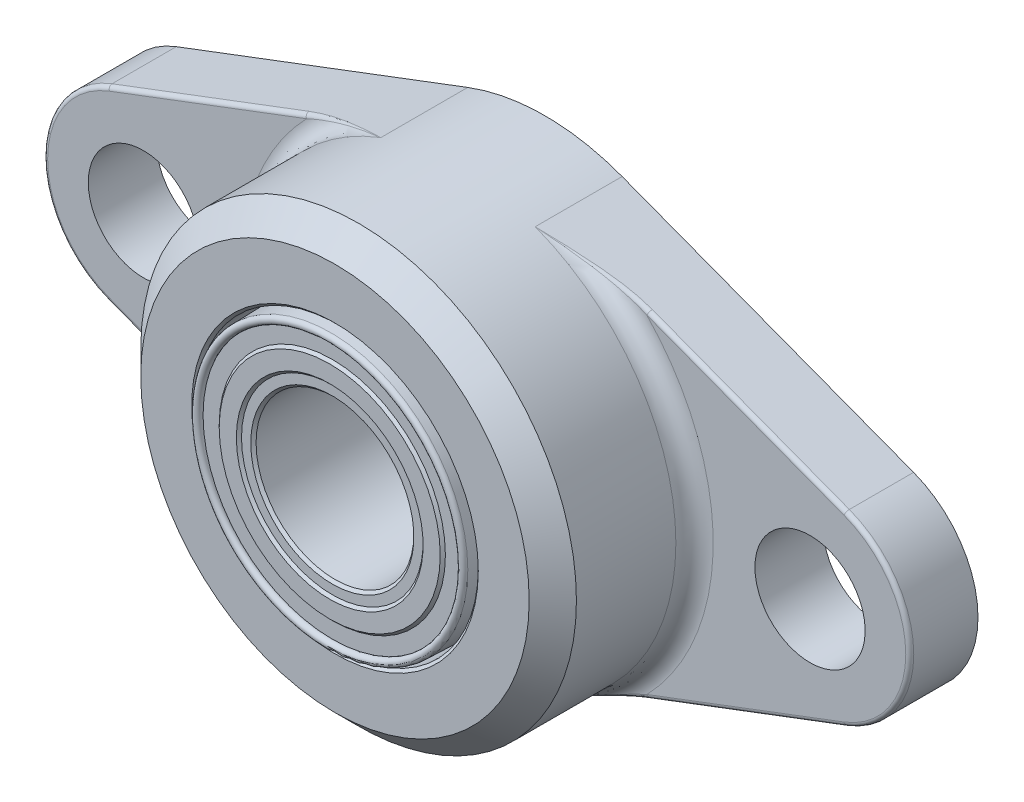
SolidWorks part; units mm, degrees
ref_plane "Front Plane" through (0, 0, 0) normal (0, 0, 1) x (1, 0, 0)
ref_plane "Top Plane" through (0, 0, 0) normal (0, 1, 0) x (1, 0, 0)
ref_plane "Right Plane" through (0, 0, 0) normal (1, 0, 0) x (0, 0, -1)
sketch "Sketch1" plane through (0, 0, 0) normal (0, 0, 1) x (1, 0, 0)
  line L0 (-31.75, 0) -> (31.75, 0) construction
  line L1 (0, 20.75) -> (0, -20.75) construction
  line L2 (-35.1161, 8.8836) -> (-7.3524, 19.4037)
  line L3 (7.3524, 19.4037) -> (35.1161, 8.8836)
  line L4 (35.1161, -8.8836) -> (7.3524, -19.4037)
  line L5 (-35.1161, -8.8836) -> (-7.3524, -19.4037)
  line L6 (-41.25, 0) -> (41.25, 0) construction
  line L7 (5.3139, 5.3139) -> (14.6725, 14.6725) construction
  circle A0 centre (-31.75, 0) radius 5.25
  circle A1 centre (31.75, 0) radius 5.25
  circle A2 centre (0, 0) radius 20.75
  arc A3 (-35.1161, 8.8836) -> (-35.1161, -8.8836) centre (-31.75, 0) ccw
  arc A4 (35.1161, -8.8836) -> (35.1161, 8.8836) centre (31.75, 0) ccw
  circle A5 centre (0, 0) radius 7.515
  circle A6 centre (0, 0) radius 13.3972 construction
  point P23 (9.4733, 9.4733)
  point P24 (0, 13.3972)
  point P25 (0, 7.515)
  dimension "Mounting Hole" = 10.5
  dimension "ID" = 15.03
  dimension "D4" = 26.7944
  dimension "Mounting Center" = 63.5
  dimension "Height" = 41.5
  dimension "Length" = 82.5
  dimension "D2" = 45
  dimension "D3" = 13.235
  dimension "D1" = 5.8822
sketch "Sketch2" plane through (0, 0, 0) normal (1, 0, 0) x (0, 0, -1)
  line L0 (10, 0) -> (-10, 0) construction
  point P2 (3.5, 0)
  point P4 (9.4, 0)
  dimension "Width" = 20
  dimension "flange thickness" = 6.5
  dimension "Bearing Width" = 19.4
sketch "Sketch3" plane through (0, 0, 0) normal (0, 0, 1) x (1, 0, 0)
  line L0 (-35.1161, 8.8836) -> (-7.3524, 19.4037) construction
  line L1 (7.3524, 19.4037) -> (35.1161, 8.8836) construction
  line L2 (35.1161, -8.8836) -> (7.3524, -19.4037) construction
  line L3 (-35.1161, -8.8836) -> (-7.3524, -19.4037) construction
  line L4 (-35.1161, 8.8836) -> (-7.3524, 19.4037)
  line L5 (7.3524, 19.4037) -> (35.1161, 8.8836)
  line L6 (35.1161, -8.8836) -> (7.3524, -19.4037)
  line L7 (-35.1161, -8.8836) -> (-7.3524, -19.4037)
  arc A0 (-35.1161, 8.8836) -> (-35.1161, -8.8836) centre (-31.75, 0) ccw construction
  circle A1 centre (-31.75, 0) radius 5.25 construction
  circle A2 centre (0, 0) radius 20.75 construction
  circle A3 centre (31.75, 0) radius 5.25 construction
  arc A4 (35.1161, -8.8836) -> (35.1161, 8.8836) centre (31.75, 0) ccw construction
  arc A5 (-35.1161, 8.8836) -> (-35.1161, -8.8836) centre (-31.75, 0) ccw
  circle A6 centre (-31.75, 0) radius 5.25
  arc A7 (-7.3524, -19.4037) -> (7.3524, -19.4037) centre (0, 0) ccw
  circle A8 centre (31.75, 0) radius 5.25
  arc A9 (35.1161, -8.8836) -> (35.1161, 8.8836) centre (31.75, 0) ccw
  circle A10 centre (0, 0) radius 13.3972 construction
  circle A11 centre (0, 0) radius 13.3972
  arc A12 (7.3524, 19.4037) -> (-7.3524, 19.4037) centre (0, 0) ccw
extrude "Boss-Extrude1" add sketch "Sketch3" along normal up to vertex (-3.5 mm away) from vertex at -10 starting at point (0, 0, -10)
sketch "Sketch4" plane through (0, 0, -3.5) normal (0, 0, 1) x (1, 0, 0)
  circle A0 centre (0, 0) radius 20.75 construction
  circle A1 centre (0, 0) radius 13.3972 construction
  circle A2 centre (0, 0) radius 20.75
  circle A3 centre (0, 0) radius 13.3972
extrude "Boss-Extrude2" add sketch "Sketch4" along normal up to vertex (13.5 mm away) up to point (0, 0, 10)
chamfer "Chamfer1" distance 0.254 angle 45 2 edges at (13.3972, 0, 10) (13.3972, 0, -10)
fillet "Fillet1" radius 1.778 2 edges
fillet "Fillet2" radius 0.381 10 edges at (12.23, 17.5555, -3.0927) (41.25, 0, -3.5) (-12.23, 17.5555, -3.0927) (-41.25, 0, -3.5) (-12.23, -17.5555, -3.0927) (12.23, -17.5555, -3.0927)
chamfer "Chamfer2" distance 2.25 angle 45 1 edges at (20.75, 0, 10)
sketch "Sketch5" plane through (0, 0, 0) normal (1, 0, 0) x (0, 0, -1)
  line L0 (-10, 7.515) -> (9.4, 7.515)
  line L1 (-10, 7.515) -> (-10, 13.3972)
  line L2 (-10, 13.3972) -> (9.4, 13.3972)
  line L3 (9.4, 13.3972) -> (9.4, 7.515)
  line L4 (-10, 0) -> (10, 0) construction
  dimension "D1" = 19.4
sketch "Sketch6" plane through (0, 0, 0) normal (1, 0, 0) x (0, 0, -1)
  line L0 (-0.3, 13.3972) -> (-10.3902, 13.0449)
  line L1 (-10.254, 12.3117) -> (-10.254, 10.7812)
  line L2 (-10.254, 10.7812) -> (-10.5, 10.7812)
  line L3 (-10.5, 10.7812) -> (-10.5, 8.6423)
  line L4 (-10.254, 7.515) -> (-10.254, 8.6423)
  line L5 (-10.254, 8.6423) -> (-10.5, 8.6423)
  line L6 (-10, 7.515) -> (9.4, 7.515) construction
  line L7 (-10, 7.515) -> (-10, 13.3972) construction
  line L8 (-10, 18.5) -> (-10, -18.5) construction
  line L9 (-10, 13.3972) -> (9.4, 13.3972) construction
  line L10 (9.154, 7.515) -> (9.154, 8.6423)
  line L11 (9.154, 8.6423) -> (9.4, 8.6423)
  line L12 (9.4, 8.6423) -> (9.4, 10.7812)
  line L13 (9.4, 10.7812) -> (6.86, 10.7812)
  line L14 (6.86, 10.7812) -> (6.86, 12.3117)
  line L15 (6.86, 12.3117) -> (9.4, 12.3117)
  line L16 (9.4, 13.3972) -> (9.4, 7.515) construction
  line L17 (9.4, 12.3117) -> (9.4, 13.3972)
  line L18 (-10.254, 7.515) -> (9.154, 7.515)
  line L19 (-0.3, 13.3972) -> (9.4, 13.3972)
  line L20 (-10, 0) -> (10, 0) construction
  arc A0 (-10.3902, 13.0449) -> (-10.254, 12.3117) centre (-10.377, 12.6681) ccw
  dimension "Bearing Width" = 19.4
  dimension "D1" = 0.5
  dimension "D2" = 0.254
  dimension "D3" = 2
  dimension "D4" = 5.8822
  dimension "D5" = 2.139
  dimension "D6" = 17.2845
  dimension "D9" = 2.54
  dimension "D7" = 0.254
revolve "Revolve1" add sketch "Sketch6" angle 360 about L20
chamfer "Chamfer3" distance 0.254 angle 45 6 edges at (8.6423, 0, -9.4) (10.7812, 0, -9.4) (10.7812, 0, 10.5) (8.6423, 0, 10.5) (7.515, 0, 10.254) (7.515, 0, -9.154)
equation "\"D1@Chamfer2\"=(\"Width@Sketch2\"-\"flange thickness@Sketch2\")/6"
equation "\"D1@Sketch1\"=\"D3@Sketch1\"/2.25"
equation "\"D1@Sketch5\"=\"Bearing Width@Sketch2\""
equation "\"D5@Sketch6\"=\"D4@Sketch6\"/2.75"
equation "\"D6@Sketch6\"=\"ID@Sketch1\"*1.15"
